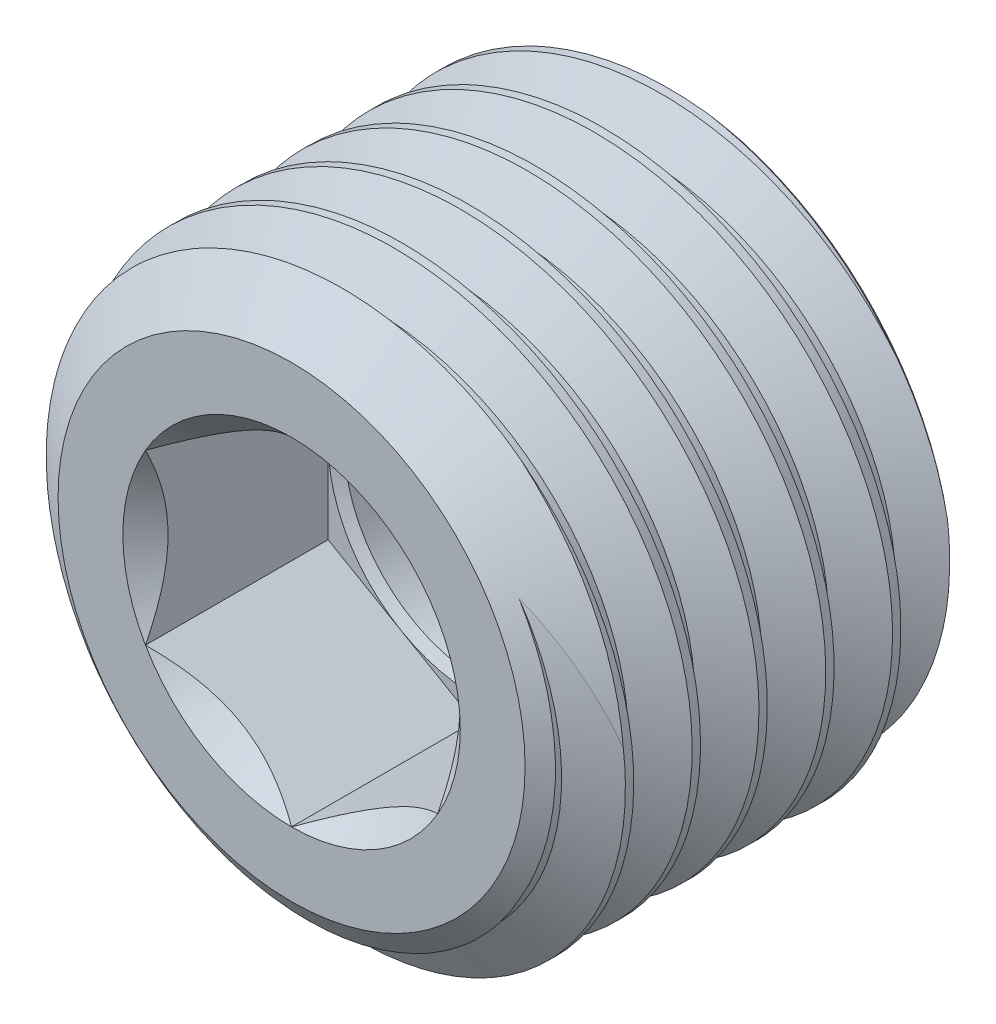
SolidWorks part; units mm, degrees
ref_plane "Front" through (0, 0, 0) normal (0, 0, 1) x (1, 0, 0)
ref_plane "Top" through (0, 0, 0) normal (0, 1, 0) x (1, 0, 0)
ref_plane "Right" through (0, 0, 0) normal (1, 0, 0) x (0, 0, -1)
sketch "Sketch22" plane through (0, 0, 0) normal (1, 0, 0) x (0, 0, -1)
  line L0 (-3.8488, 0) -> (-3.8488, 4.4399)
  line L1 (-3.8488, 4.4399) -> (-3.0716, 5.5499)
  line L2 (-3.0716, 5.5499) -> (3.1674, 5.5499)
  line L3 (3.1674, 5.5499) -> (5.6762, 3.0412)
  line L4 (5.6762, 3.0412) -> (3.8488, 0)
  line L5 (3.8488, 0) -> (-3.8488, 0)
  line L6 (3.8488, 0) -> (5.6762, 0) construction
  line L7 (5.6762, 0) -> (5.6762, 3.0412) construction
  line L8 (5.6762, -3.0412) -> (3.8488, 0) construction
  line L9 (-3.0716, -5.5499) -> (3.1674, -5.5499) construction
  dimension "Dia" = 11.0998
  dimension "Length" = 9.525
  dimension "D3" = 35
  dimension "D5" = 118
  dimension "D6" = 45
  dimension "D7" = 8.8798
revolve "Revolve1" add sketch "Sketch22" angle 360 about L6
ref_plane "Plane1" through (0, 0, -5.6762) normal (0, 0, 1) x (1, 0, 0)
sketch "Sketch27" plane through (0, 0, -5.6762) normal (0, 0, 1) x (1, 0, 0)
  circle A0 centre (0, 0) radius 5.5499 construction
  circle A1 centre (0, 0) radius 5.5499
curve "Helix/Spiral1" pitch 1.27 height 12.6492 radius 5.5499 centre (0, 0, -5.6762) axis (0, 0, 1) start towards (1, 0, 0)
sketch "Sketch28" plane through (0, 0, 0) normal (1, 0, 0) x (0, 0, -1)
  line L0 (5.6762, 5.5499) -> (6.7874, 5.5499)
  line L1 (6.7874, 5.5499) -> (6.3429, 4.78)
  line L2 (6.3429, 4.78) -> (6.1207, 4.78)
  line L3 (6.1207, 4.78) -> (5.6762, 5.5499)
  line L4 (5.8984, 5.165) -> (6.5652, 5.165) construction
  line L6 (-3.0716, 5.5499) -> (3.1674, 5.5499) construction
  line L7 (5.6762, 14.1602) -> (5.6762, -14.1602) construction
  dimension "D1" = 0.2222
  dimension "D3" = 60
  dimension "D2" = 1.1113
sweep "Cut-Sweep2" cut profiles "Sketch28" path "Helix/Spiral1" align with end faces yes
sketch "Sketch23" plane through (0, 0, 3.8488) normal (0, 0, 1) x (1, 0, 0)
  line L1 (0, 3.2079) -> (-2.7781, 1.604)
  line L2 (-2.7781, 1.604) -> (-2.7781, -1.604)
  line L3 (-2.7781, -1.604) -> (0, -3.2079)
  line L4 (0, -3.2079) -> (2.7781, -1.604)
  line L5 (2.7781, -1.604) -> (2.7781, 1.604)
  line L6 (2.7781, 1.604) -> (0, 3.2079)
  circle A0 centre (0, 0) radius 2.7781 construction
  dimension "Hex" = 5.5562
extrude "Cut-Extrude10" cut sketch "Sketch23" against normal blind 3.4727
sketch "Sketch24" plane through (0, 0, 3.8488) normal (0, 0, 1) x (1, 0, 0)
  circle A0 centre (0, 0) radius 3.2079
extrude "Cut-Extrude11" cut sketch "Sketch24" against normal through all draft 45
sketch "Sketch26" plane through (0, 0, 0.3762) normal (0, 0, 1) x (1, 0, 0)
  circle A0 centre (0, 0) radius 2.7781 construction
  circle A1 centre (0, 0) radius 2.7781
extrude "Cut-Extrude12" cut sketch "Sketch26" against normal through all draft 60
sketch "Sketch30" plane through (0, 0, 0) normal (1, 0, 0) x (0, 0, -1)
  line L0 (-3.0716, 5.5499) -> (3.1674, 5.5499) construction
  line L1 (-3.8488, 0) -> (-3.8488, 4.4399) construction
  line L2 (5.6762, 0) -> (5.6762, 3.0412) construction
  line L3 (-3.0716, -5.5499) -> (3.1674, -5.5499) construction
  point P0 (-3.8488, 5.5499)
  point P1 (5.6762, 5.5499)
  point P2 (5.6762, -5.5499)
  point P11 (2.5012, -5.5499)
  dimension "D1" = 3.175
sketch "Sketch31" plane through (0, 0, 0) normal (1, 0, 0) x (0, 0, -1)
  line L2 (3.8488, 0) -> (5.6762, -3.0412)
  line L3 (5.6762, 3.0412) -> (3.8488, 0)
hole_wizard "13/64 (0.20313) Diameter Hole1" positions "Sketch33" profile "Sketch34" hole size "13/64" standard "ANSI Inch" end condition through all
sketch "Sketch33" plane through (0, 0, 3.8488) normal (0, 0, 1) x (1, 0, 0)
  point P0 (0, 0)
sketch "Sketch34" plane through (0, 0, 3.8488) normal (1, 0, 0) x (0, -1, 0)
  line L0 (0, 0) -> (0, 9.525)
  line L1 (0, 9.525) -> (2.5798, 9.525)
  line L2 (2.5798, 9.525) -> (2.5798, 0)
  line L5 (2.5798, 0) -> (0, 0)
  line L11 (0, -6.35) -> (0, 107.95) construction
  dimension "Thru Hole Dia." = 5.1595
  dimension "Thru Hole Depth" = 9.525
sketch "Sketch35" plane through (0, 0, 0) normal (1, 0, 0) x (0, 0, -1)
  line L0 (-3.8488, 4.4399) -> (-3.8488, -4.4399) construction
  line L1 (3.2251, 0) -> (7.7619, 0)
  line L2 (3.2251, 0) -> (3.2251, 7.63)
  line L3 (3.2251, 7.63) -> (7.7619, 7.63)
  line L4 (7.7619, 0) -> (7.7619, 7.63)
  line L5 (3.2251, 0) -> (0, 0) construction
  dimension "D1" = 7.0739
revolve "Cut-Revolve1" cut sketch "Sketch35" angle 360 about L5
equation "\"D7@Sketch22\"=\"Dia@Sketch22\"*.8"
equation "\"D1@Sketch28\" = \"D4@Helix/Spiral1\" * .175"
equation "\"D3@Helix/Spiral1\" = \"Length@Sketch22\" + .123"
equation "\"D1@Sketch30\" = \"D4@Helix/Spiral1\" * 2.5"
equation "\"hex Depth@Cut-Extrude10\" = \"Hex@Sketch23\" * .625"
equation "\"D2@Sketch28\" = \"D4@Helix/Spiral1\" * .875"
